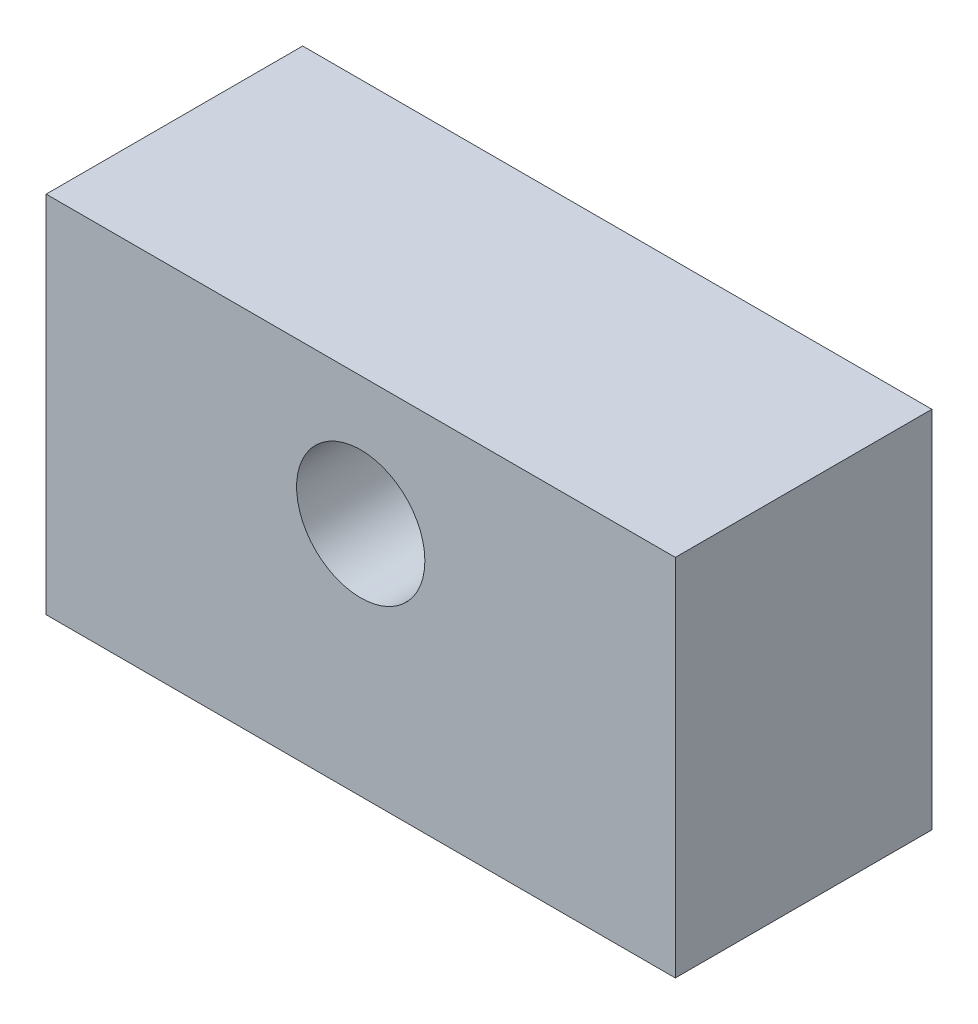
SolidWorks part; units mm, degrees
material "1060 Alloy"
ref_plane "Front" through (0, 0, 0) normal (0, 0, 1) x (1, 0, 0)
ref_plane "Top" through (0, 0, 0) normal (0, 1, 0) x (1, 0, 0)
ref_plane "Right" through (0, 0, 0) normal (1, 0, 0) x (0, 0, -1)
sketch "Sketch3" plane through (0, 0, 0) normal (0, 0, 1) x (1, 0, 0)
  line L0 (-0.127, -6.35) -> (30.1755, -6.35)
  line L1 (0, 0) -> (31.1484, 0)
  line L2 (0, 0) -> (0, -19.8376)
  line L3 (0, -19.8376) -> (31.1484, -19.8376)
  line L4 (31.1484, 0) -> (31.1484, -19.8376)
  line L5 (15.5742, -19.8376) -> (15.5742, 0) construction
  line L6 (15.5742, -6.35) -> (8.0621, -19.3614) construction
  line L15 (12.5496, -11.5887) -> (15.5742, -13.335) construction
  line L16 (15.5742, -6.35) -> (22.9274, -19.0862) construction
  circle A0 centre (15.5742, -6.35) radius 6.0492 construction
  point P14 (0, -6.35)
  point P17 (9.525, -6.35)
  point P19 (31.1484, -6.35)
  point P20 (7.7871, -19.8376)
  point P24 (23.3613, -19.8376)
  dimension "D2" = 6.35
  dimension "D6" = 3.4925
  dimension "D3" = 60
  dimension "D1" = 9.525
  dimension "D4" = 9.525
  dimension "D5" = 60
extrude "Boss-Extrude1" add sketch "Sketch3" along normal mid plane 12.7
sketch "Sketch4" plane through (0, 0, 0) normal (-1, 0, 0) x (0, 0, 1)
  circle A0 centre (0, -6.35) radius 3.175
  dimension "D1" = 6.35
extrude "Cut-Extrude1" cut sketch "Sketch4" against normal blind 9.525
ref_plane "Plane1" through (7.7871, -19.8376, 0) normal (-0.5, -0.866, 0) x (-0.866, 0.5, 0)
ref_plane "Mirror Plane" through (15.5742, 0, 0) normal (-1, 0, 0) x (0, 0, 1)
sketch "Sketch5" plane through (7.7871, -19.8376, 0) normal (-0.5, -0.866, 0) x (-0.866, 0.5, 0)
  circle A0 centre (0, 0) radius 3.175
  dimension "D1" = 6.35
extrude "Cut-Extrude5" cut sketch "Sketch5" against normal blind 9.525 and the other way up to next
sketch "Sketch6" plane through (0, 0, 6.35) normal (0, 0, -1) x (-1, 0, 0)
  circle A0 centre (-15.5742, -6.35) radius 3.175
  dimension "D1" = 6.35
extrude "Cut-Extrude6" cut sketch "Sketch6" along normal blind 9.525
mirror "Mirror1" about plane through (15.5742, 0, 0) normal (-1, 0, 0) of "Cut-Extrude5"
sketch "Sketch7" plane through (31.1484, 0, 0) normal (1, 0, 0) x (0, 0, -1)
  line L0 (6.35, -19.8376) -> (6.35, 0) construction
  line L1 (-6.35, -19.8376) -> (6.35, -19.8376)
  line L2 (-6.35, -19.8376) -> (-6.35, -18.034)
  line L3 (-6.35, -18.034) -> (6.35, -18.034)
  line L4 (6.35, -19.8376) -> (6.35, -18.034)
  line L5 (-6.35, 0) -> (6.35, 0) construction
  dimension "D1" = 18.034
extrude "Cut-Extrude7" cut sketch "Sketch7" against normal through all
equation "\"truss_member_od\" = .25in"
equation "\"truss_member_id\"= 0in"
equation "\"truss_member_L1\" = 2.125in"
equation "\"connector_hole_depth\" = .375in"
equation "\"D1@Boss-Extrude1\"=\"truss_member_od\"*2"
equation "\"D6@Sketch3\"=\"truss_member_od\"/2*1.1"
equation "\"D1@Sketch4\"=\"truss_member_od\""
equation "\"D1@Cut-Extrude1\"=\"connector_hole_depth\""
equation "\"D1@Sketch3\"=\"connector_hole_depth\""
equation "\"D4@Sketch3\"=\"connector_hole_depth\""
equation "\"D1@Sketch5\"=\"truss_member_od\""
equation "\"D1@Cut-Extrude5\"=\"connector_hole_depth\""
equation "\"D1@Cut-Extrude6\"=\"connector_hole_depth\""
equation "\"D1@Sketch6\"=\"truss_member_od\""
